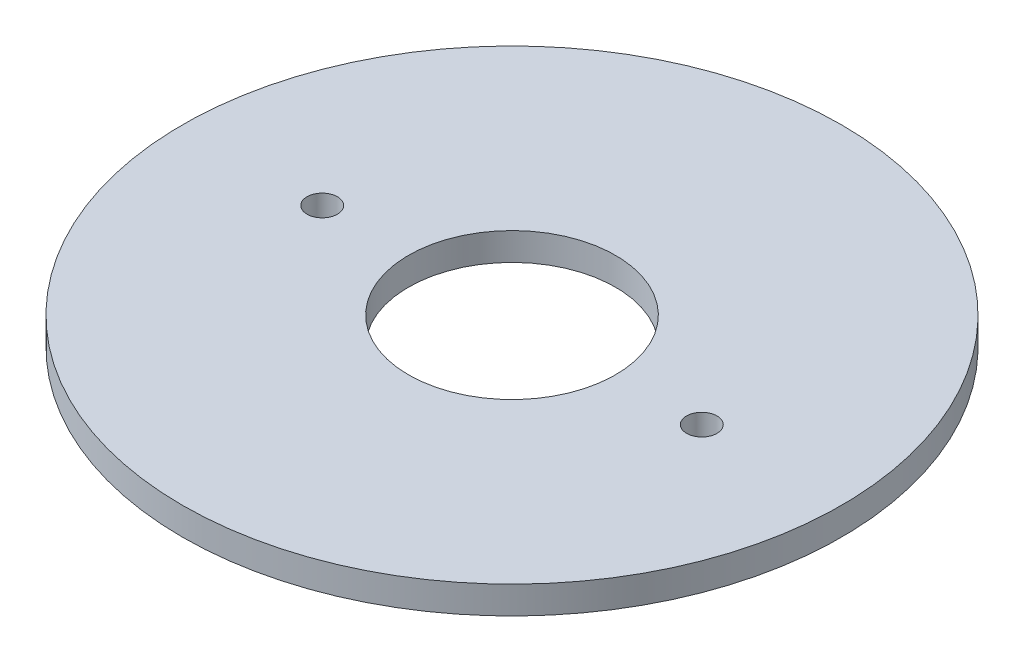
SolidWorks part; units mm, degrees
material "Balsa"
ref_plane "Front Plane" through (0, 0, 0) normal (0, 0, 1) x (1, 0, 0)
ref_plane "Top Plane" through (0, 0, 0) normal (0, 1, 0) x (1, 0, 0)
ref_plane "Right Plane" through (0, 0, 0) normal (1, 0, 0) x (0, 0, -1)
sketch "Sketch1" plane through (0, 0, 0) normal (0, 1, 0) x (1, 0, 0)
  line L0 (-47.75, 0) -> (47.75, 0) construction
  line L1 (0, 47.75) -> (0, -47.75) construction
  line L2 (47.75, 84.8597) -> (47.75, -119.3895) construction
  circle A0 centre (0, 0) radius 47.75
  circle A1 centre (-27.5, 0) radius 2.2
  circle A2 centre (27.5, 0) radius 2.2
  circle A3 centre (0, 0) radius 15
  dimension "D1" = 55
  dimension "D2" = 4.4
  dimension "D3" = 95.5
  dimension "D4" = 30
extrude "Boss-Extrude1" add sketch "Sketch1" along normal blind 4
